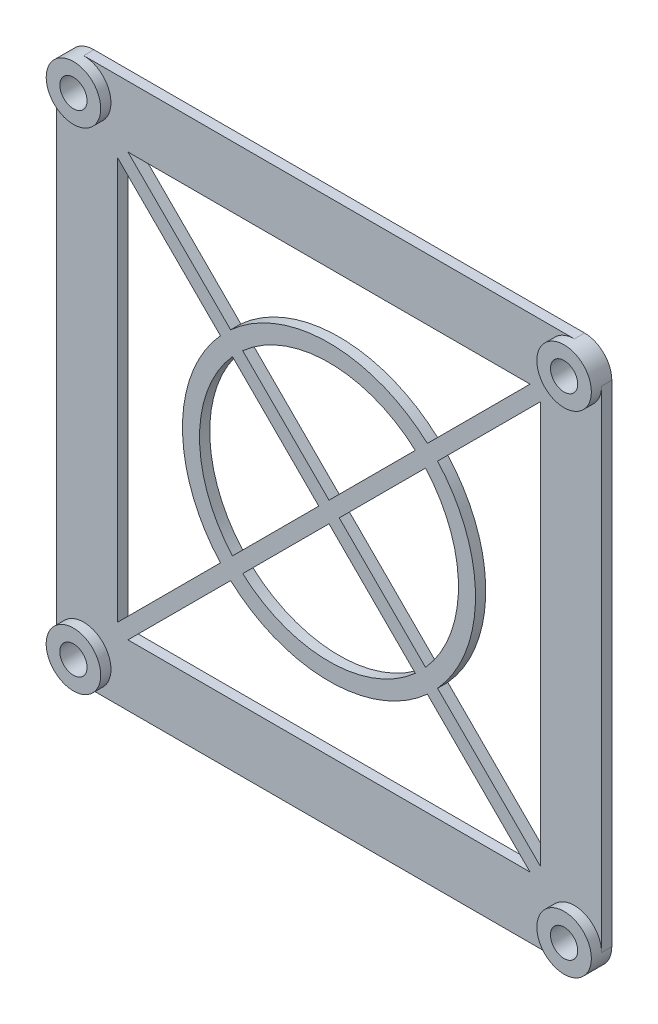
SolidWorks part; units mm, degrees
ref_plane "Front Plane" through (0, 0, 0) normal (0, 0, 1) x (1, 0, 0)
ref_plane "Top Plane" through (0, 0, 0) normal (0, 1, 0) x (1, 0, 0)
ref_plane "Right Plane" through (0, 0, 0) normal (1, 0, 0) x (0, 0, -1)
sketch "Sketch1" plane through (0, 0, 0) normal (0, 0, 1) x (1, 0, 0)
  line L1 (0, 0) -> (80, 0)
  line L2 (0, 0) -> (0, 80)
  line L3 (0, 80) -> (80, 80)
  line L4 (80, 0) -> (80, 80)
  dimension "D1" = 80
  dimension "D2" = 80
extrude "Boss-Extrude1" add sketch "Sketch1" along normal blind 1.5 contours L2 L3 L4 L1
fillet "Fillet1" radius 4 4 edges at (0, 0, 0.75) (80, 0, 0.75) (80, 80, 0.75) (0, 80, 0.75)
sketch "Sketch2" plane through (0, 0, 1.5) normal (0, 0, 1) x (1, 0, 0)
  circle A0 centre (4, 76) radius 4
  circle A1 centre (76, 76) radius 4
  circle A2 centre (4, 4) radius 4
  circle A3 centre (76, 4) radius 4
extrude "Boss-Extrude2" add sketch "Sketch2" along normal blind 1.5
hole_wizard "Ø4.0mm Dowel Hole1" positions "Sketch3" profile "Sketch4" hole size "Ø4.0" standard "ANSI Metric" end condition through all
sketch "Sketch3" plane through (0, 0, 0) normal (0, 0, -1) x (-1, 0, 0)
  point P0 (-4, 4)
  point P3 (-76, 4)
  point P6 (-76, 76)
  point P9 (-4, 76)
sketch "Sketch4" plane through (4, 4, 0) normal (1, 0, 0) x (0, 1, 0)
  line L0 (0, 0) -> (0, 3)
  line L1 (0, 3) -> (2, 3)
  line L2 (2, 3) -> (2, 0)
  line L5 (2, 0) -> (0, 0)
  line L11 (0, -6.35) -> (0, 107.95) construction
  dimension "Thru Hole Dia." = 4
  dimension "Thru Hole Depth" = 3
sketch "Sketch5" plane through (0, 0, 0) normal (0, 0, -1) x (-1, 0, 0)
  line L0 (-4, 80) -> (-76, 80) construction
  line L1 (-71, 71) -> (-9, 71)
  line L2 (-71, 71) -> (-71, 9)
  line L3 (-71, 9) -> (-9, 9)
  line L4 (-9, 71) -> (-9, 9)
  line L5 (0, 4) -> (0, 76) construction
  line L6 (-4, 0) -> (-76, 0) construction
  line L7 (-80, 4) -> (-80, 76) construction
  line L8 (-71, 10.5) -> (-55.9343, 25.5657)
  line L9 (-69.5, 9) -> (-54.4343, 24.0657)
  line L10 (-10.5, 9) -> (-25.5657, 24.0657)
  line L11 (-9, 10.5) -> (-24.0657, 25.5657)
  line L12 (-41.5, 40) -> (-54.1641, 52.6641)
  line L13 (-40, 41.5) -> (-52.6641, 54.1641)
  line L14 (-40, 41.5) -> (-27.3359, 54.1641)
  line L15 (-38.5, 40) -> (-25.8359, 52.6641)
  line L16 (-24.0657, 54.4343) -> (-9, 69.5)
  line L17 (-25.5657, 55.9343) -> (-10.5, 71)
  line L18 (-54.4343, 55.9343) -> (-69.5, 71)
  line L19 (-55.9343, 54.4343) -> (-71, 69.5)
  line L20 (-52.6641, 25.8359) -> (-40, 38.5)
  line L21 (-54.1641, 27.3359) -> (-41.5, 40)
  line L22 (-25.8359, 27.3359) -> (-38.5, 40)
  line L23 (-27.3359, 25.8359) -> (-40, 38.5)
  arc A0 (-27.3359, 54.1641) -> (-52.6641, 54.1641) centre (-40, 40) ccw
  arc A1 (-25.5657, 55.9343) -> (-54.4343, 55.9343) centre (-40, 40) ccw
  arc A2 (-54.1641, 52.6641) -> (-54.1641, 27.3359) centre (-40, 40) ccw
  arc A3 (-55.9343, 54.4343) -> (-55.9343, 25.5657) centre (-40, 40) ccw
  arc A4 (-52.6641, 25.8359) -> (-27.3359, 25.8359) centre (-40, 40) ccw
  arc A5 (-54.4343, 24.0657) -> (-25.5657, 24.0657) centre (-40, 40) ccw
  arc A6 (-24.0657, 25.5657) -> (-24.0657, 54.4343) centre (-40, 40) ccw
  arc A7 (-25.8359, 27.3359) -> (-25.8359, 52.6641) centre (-40, 40) ccw
  dimension "D15" = 38
  dimension "D1" = 9
  dimension "D2" = 9
  dimension "D3" = 9
  dimension "D4" = 9
  dimension "D5" = 1.5
  dimension "D6" = 1.5
  dimension "D7" = 1.5
  dimension "D8" = 1.5
  dimension "D9" = 1.5
  dimension "D10" = 1.5
  dimension "D11" = 1.5
  dimension "D12" = 1.5
  dimension "D13" = 31
  dimension "D14" = 31
extrude "Cut-Extrude1" cut sketch "Sketch5" against normal blind 1.5 contours A3 L19 L2 L8 | L12 A2 L21 | L14 A0 L13 | A1 L17 L1 L18 | A6 L11 L4 L16 | L22 A7 L15 | L20 A4 L23 | A5 L9 L3 L10 region at (40, 65.5553, 0) region at (65.5553, 40, 0) region at (14.4447, 40, 0) region at (40, 14.4447, 0) region at (52.0663, 40, 0) region at (40, 52.0663, 0) region at (27.9337, 40, 0) region at (40, 27.9337, 0)
